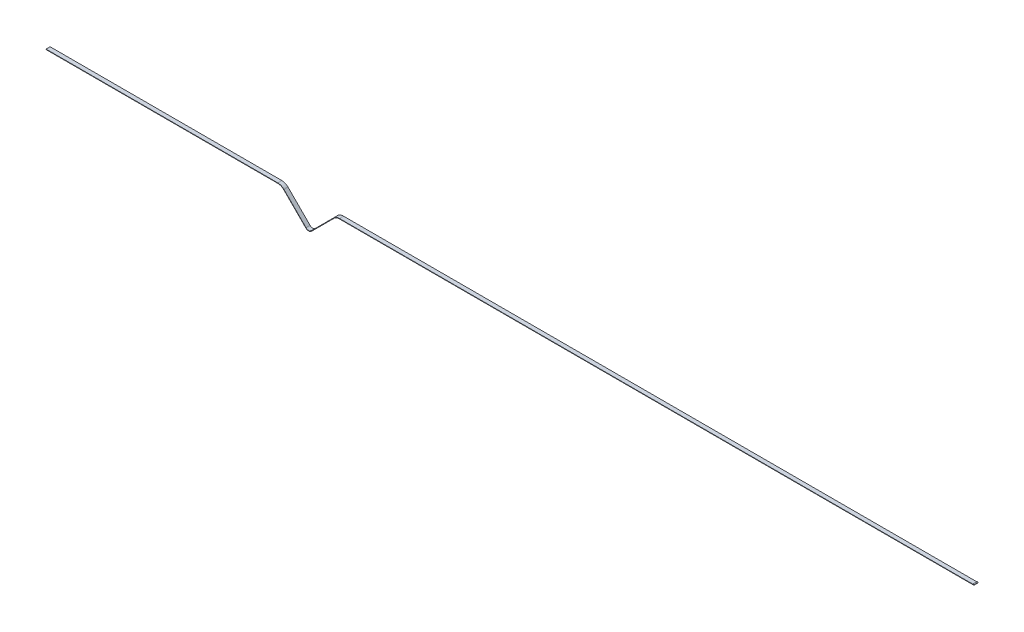
SolidWorks part; units mm, degrees
ref_plane "Front Plane" through (0, 0, 0) normal (0, 0, 1) x (1, 0, 0)
ref_plane "Top Plane" through (0, 0, 0) normal (0, 1, 0) x (1, 0, 0)
ref_plane "Right Plane" through (0, 0, 0) normal (1, 0, 0) x (0, 0, -1)
sketch "Sketch1" plane through (0, 0, 0) normal (1, 0, 0) x (0, 0, -1)
  line L1 (0, 0) -> (6, 0)
  line L2 (0, 0) -> (0, 0.63)
  line L3 (0, 0.63) -> (6, 0.63)
  line L4 (6, 0) -> (6, 0.63)
  dimension "D1" = 0.63
  dimension "D2" = 6
sketch "Sketch2" plane through (0, 0, 0) normal (0, 0, 1) x (1, 0, 0)
  line L0 (0, 0) -> (-937.7651, 0)
  line L1 (-946.2202, -3.5053) -> (-979.012, -36.3377)
  line L2 (-987.6582, -36.3377) -> (-1020.4499, -3.5053)
  line L3 (-1028.9051, 0) -> (-1371.6, 0)
  arc A0 (-937.7651, 0) -> (-946.2202, -3.5053) centre (-937.7651, -11.95) ccw
  arc A1 (-979.012, -36.3377) -> (-987.6582, -36.3377) centre (-983.3351, -32.02) cw
  arc A2 (-1020.4499, -3.5053) -> (-1028.9051, 0) centre (-1028.9051, -11.95) ccw
  dimension "D1" = 6.11
  dimension "D4" = 1371.6
sweep "Sweep1" add profiles "Sketch1" path "Sketch2"
sketch "Sketch3" plane through (0, 0, 0) normal (0, 0, 1) x (1, 0, 0)
  line L0 (0, 0.63) -> (-937.7651, 0.63) construction
  line L1 (-1.5, 0.63) -> (-1.5, 0)
  line L2 (0, 0) -> (-937.7651, 0) construction
  line L3 (-1.5, 0) -> (0, 0)
  line L4 (0, 0) -> (0, 0.63)
  arc A1 (0, 0.63) -> (-1.5, 0.63) centre (-0.75, 0.63) ccw
  dimension "D1" = 0.75
extrude "Boss-Extrude1" add sketch "Sketch3" against normal through all
pattern_curve "CrvPattern1" [suppressed] of bodies 102 driven by "Sketch2" parameters "D1"=2000, "D3"=2, "D2"=1, "D4"=10
